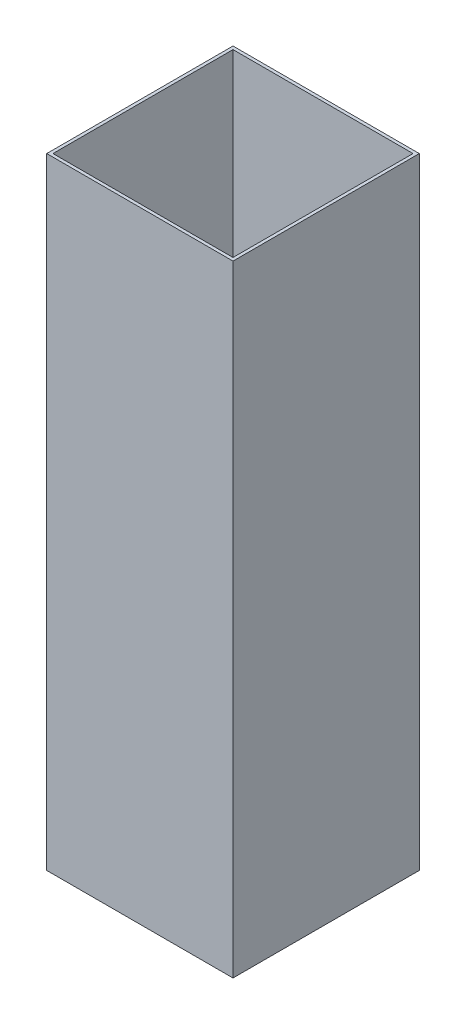
SolidWorks part; units mm, degrees
ref_plane "Front" through (0, 0, 0) normal (0, 0, 1) x (1, 0, 0)
ref_plane "Top" through (0, 0, 0) normal (0, 1, 0) x (1, 0, 0)
ref_plane "Right" through (0, 0, 0) normal (1, 0, 0) x (0, 0, -1)
sketch "Sketch1" plane through (0, 0, 0) normal (0, 1, 0) x (1, 0, 0)
  line L0 (-73.66, 73.66) -> (73.66, 73.66)
  line L1 (-76.2, 76.2) -> (76.2, 76.2)
  line L2 (-76.2, 76.2) -> (-76.2, -76.2)
  line L3 (-76.2, -76.2) -> (76.2, -76.2)
  line L4 (76.2, 76.2) -> (76.2, -76.2)
  line L5 (-76.2, 76.2) -> (76.2, -76.2) construction
  line L6 (-76.2, -76.2) -> (76.2, 76.2) construction
  line L7 (73.66, 73.66) -> (73.66, -73.66)
  line L8 (-73.66, -73.66) -> (73.66, -73.66)
  line L9 (-73.66, 73.66) -> (-73.66, -73.66)
  point P0 (0, 0)
  dimension "D1" = 152.4
  dimension "D2" = 152.4
  dimension "D3" = 2.54
extrude "Boss-Extrude1" add sketch "Sketch1" along normal blind 6604
sketch "Sketch2" [suppressed] plane through (0, 0, 76.2) normal (0, 0, 1) x (1, 0, 0)
  line L0 (76.2, 6019.8) -> (76.2, 0) construction
  line L1 (-76.2, 6019.8) -> (76.2, 6019.8)
  line L2 (-76.2, 6019.8) -> (-76.2, 2336.8)
  line L3 (-76.2, 2336.8) -> (76.2, 2336.8)
  line L4 (76.2, 6019.8) -> (76.2, 2336.8)
  dimension "D1" = 2336.8
extrude "Cut-Extrude1" [suppressed] cut sketch "Sketch2" against normal through all
sketch "Sketch3" plane through (0, 0, 0) normal (0, -1, 0) x (1, 0, 0)
  line L4 (76.2, -76.2) -> (76.2, 76.2)
  line L5 (76.2, 76.2) -> (-76.2, 76.2)
  line L6 (-76.2, 76.2) -> (-76.2, -76.2)
  line L7 (-76.2, -76.2) -> (76.2, -76.2)
  line L8 (76.2, -76.2) -> (76.2, 76.2)
  line L9 (76.2, 76.2) -> (-76.2, 76.2)
  line L10 (-76.2, 76.2) -> (-76.2, -76.2)
  line L11 (-76.2, -76.2) -> (76.2, -76.2)
  dimension "D1" = 0
extrude "Cut-Extrude2" cut sketch "Sketch3" against normal offset from surface (6096 mm away) 508 up to face at (0, 6604, 0)
